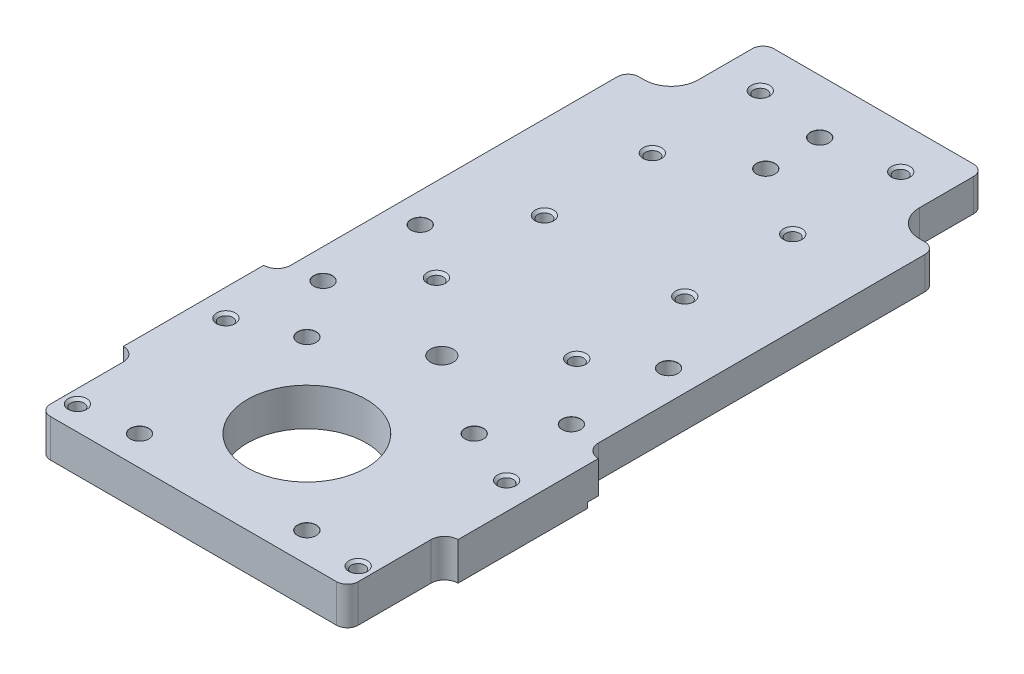
SolidWorks part; units mm, degrees
ref_plane "Top" through (0, 0, 0) normal (0, 0, 1) x (1, 0, 0)
ref_plane "Front" through (0, 0, 0) normal (0, 1, 0) x (1, 0, 0)
ref_plane "Right" through (0, 0, 0) normal (1, 0, 0) x (0, 0, -1)
sketch "Plate Main Sketch" plane through (-158.0855, 0, 24.6791) normal (0, 1, 0) x (-1, 0, 0)
  line L1 (-178.5855, -24.6791) -> (-137.5855, -24.6791)
  line L2 (-127.0855, 57.3209) -> (-127.0855, 83.3209)
  line L3 (-129.5855, 101.3209) -> (-186.5855, 101.3209)
  line L4 (-129.5855, 101.3209) -> (-129.5855, 85.8209)
  line L5 (-158.0855, 101.3209) -> (-158.0855, -24.6791) construction
  line L6 (-178.5855, -12.6791) -> (-178.5855, -24.6791)
  line L7 (-129.5855, 54.8209) -> (-129.5855, -7.6791)
  line L8 (-129.5855, -7.6791) -> (-132.5855, -7.6791)
  line L9 (-137.5855, -12.6791) -> (-137.5855, -24.6791)
  line L10 (-186.5855, -7.6791) -> (-183.5855, -7.6791)
  line L11 (-186.5855, 54.8209) -> (-186.5855, -7.6791)
  line L12 (-189.0855, 57.3209) -> (-189.0855, 83.3209)
  line L13 (-186.5855, 101.3209) -> (-186.5855, 85.8209)
  arc A0 (-129.5855, 85.8209) -> (-127.0855, 83.3209) centre (-127.0855, 85.8209) ccw
  arc A1 (-129.5855, 54.8209) -> (-127.0855, 57.3209) centre (-127.0855, 54.8209) cw
  arc A2 (-132.5855, -7.6791) -> (-137.5855, -12.6791) centre (-132.5855, -12.6791) ccw
  arc A3 (-183.5855, -7.6791) -> (-178.5855, -12.6791) centre (-183.5855, -12.6791) cw
  arc A4 (-186.5855, 54.8209) -> (-189.0855, 57.3209) centre (-189.0855, 54.8209) ccw
  arc A5 (-186.5855, 85.8209) -> (-189.0855, 83.3209) centre (-189.0855, 85.8209) cw
  circle A18 centre (-158.0855, 80.3209) radius 11
  circle A19 centre (-158.0855, 55.3209) radius 2.1117
  point P27 (0, 0)
  dimension "D2" = 5
  dimension "D8" = 22
  dimension "D1" = 2.5
  dimension "D3" = 62
  dimension "D4" = 126
  dimension "D5" = 18
  dimension "D6" = 44
  dimension "D15" = 21
  dimension "D16" = 46
  dimension "D17" = 8
  dimension "D7" = 109
extrude "Extrude Plate Main" add sketch "Plate Main Sketch" along normal blind 7
fillet "Fillet1" radius 2 6 edges at (-28.5, 3.5, 126) (-28.5, 3.5, 17) (-20.5, 3.5, 0) (20.5, 3.5, 0) (28.5, 3.5, 17) (28.5, 3.5, 126)
sketch "Reccess Sketch" plane through (0, 0, 0) normal (0, 1, 0) x (1, 0, 0)
  line L0 (-8.25, 0) -> (-8.25, -81)
  line L1 (-11.25, -84) -> (-31, -84)
  line L2 (-31, -84) -> (-31, 0)
  line L3 (-31, 0) -> (-8.25, 0)
  line L4 (0, 0) -> (0, -84) construction
  line L5 (31, 0) -> (8.25, 0)
  line L6 (8.25, 0) -> (8.25, -81)
  line L7 (31, -84) -> (31, 0)
  line L8 (11.25, -84) -> (31, -84)
  arc A0 (-8.25, -81) -> (-11.25, -84) centre (-11.25, -81) cw
  arc A1 (8.25, -81) -> (11.25, -84) centre (11.25, -81) ccw
  point P7 (-8.25, -84)
  point P10 (0, 0)
  dimension "D4" = 3
  dimension "D1" = 84
  dimension "D2" = 31
  dimension "D3" = 22.75
hole_wizard "M3x0.5 Tapped Hole3" positions "Sketch12" profile "Sketch13" tap size "M3x0.5" standard "ANSI Metric" end condition through all
sketch "Sketch12" plane through (0, 0, 0) normal (0, -1, 0) x (-1, 0, 0)
  line L0 (-13, -8) -> (-13, -68) construction
  line L2 (13, -68) -> (13, -8) construction
  line L4 (26, -121.5) -> (-26, -121.5) construction
  line L5 (-26, -121.5) -> (-26, -94) construction
  line L6 (-26, -94) -> (26, -94) construction
  line L7 (26, -94) -> (26, -121.5) construction
  line L11 (31, -126) -> (-31, -126) construction
  line L12 (31, -126) -> (31, 0) construction
  line L13 (31, 0) -> (-31, 0) construction
  line L14 (-31, -126) -> (-31, 0) construction
  line L15 (0, 0) -> (0, -126) construction
  line L16 (31, -63) -> (-31, -63) construction
  point P0 (-26, -121.5)
  point P2 (-26, -94)
  point P4 (26, -94)
  point P8 (13, -68)
  point P10 (13, -48)
  point P12 (13, -28)
  point P14 (13, -8)
  point P16 (-13, -8)
  point P18 (-13, -28)
  point P20 (-13, -48)
  point P22 (-13, -68)
  point P477 (26, -121.5)
  point P479 (0, 0)
  point P481 (0, 0)
  point P482 (0, 0)
  point P483 (0, 0)
  point P484 (0, 0)
  point P485 (0, -63)
  point P486 (0, 0)
  point P487 (21.3881, -116.3693)
  point P488 (0, 0)
  point P489 (0, 0)
  dimension "D1" = 126
  dimension "D2" = 62
  dimension "D3" = 118
  dimension "D4" = 98
  dimension "D5" = 78
  dimension "D6" = 58
  dimension "D7" = 18
  dimension "D8" = 18
  dimension "D9" = 5
  dimension "D10" = 5
  dimension "D11" = 4.5
  dimension "D12" = 32
sketch "Sketch13" plane through (26, 0, 121.5) normal (1, 0, 0) x (0, 0, -1)
  line L0 (0, 0) -> (0, 7)
  line L1 (0, 7) -> (1.725, 7)
  line L2 (1.25, 6.525) -> (1.25, 0)
  line L5 (1.25, 0) -> (0, 0)
  line L7 (1.725, 7) -> (1.25, 6.525)
  line L8 (-1.725, 7) -> (-1.25, 6.525) construction
  line L11 (0, -6.35) -> (0, 107.95) construction
  dimension "Thru Tap Drill Dia." = 2.5
  dimension "Thru Tap Drill Depth" = 7
  dimension "Far C'Sink Dia." = 3.45
  dimension "Far C'Sink Angle" = 90
cosmetic thread "Hole Thread54" parameters "D2"=3
cosmetic thread "Hole Thread55" parameters "D2"=3
cosmetic thread "Hole Thread56" parameters "D2"=3
cosmetic thread "Hole Thread57" parameters "D2"=3
cosmetic thread "Hole Thread58" parameters "D2"=3
cosmetic thread "Hole Thread59" parameters "D2"=3
cosmetic thread "Hole Thread60" parameters "D2"=3
cosmetic thread "Hole Thread61" parameters "D2"=3
cosmetic thread "Hole Thread62" parameters "D2"=3
cosmetic thread "Hole Thread63" parameters "D2"=3
cosmetic thread "Hole Thread64" parameters "D2"=3
cosmetic thread "Hole Thread65" parameters "D2"=3
hole_wizard "CBORE for M3 SHCS1" positions "Sketch4" profile "Sketch5" counterbore size "M3" standard "ANSI Metric" end condition through all
sketch "Sketch4" plane through (0, 0, 0) normal (0, -1, 0) x (-1, 0, 0)
  line L0 (31, -126) -> (-31, -126) construction
  line L1 (-31, -126) -> (-31, 0) construction
  line L2 (-31, 0) -> (31, 0) construction
  line L3 (31, 0) -> (31, -126) construction
  line L5 (15.5, -120.5) -> (-15.5, -120.5) construction
  line L6 (-15.5, -120.5) -> (-15.5, -89.5) construction
  line L7 (-15.5, -89.5) -> (15.5, -89.5) construction
  line L8 (15.5, -89.5) -> (15.5, -120.5) construction
  line L10 (0, -126) -> (0, 0) construction
  point P0 (15.5, -120.5)
  point P3 (-15.5, -120.5)
  point P6 (-15.5, -89.5)
  point P9 (15.5, -89.5)
  point P12 (23, -79)
  point P15 (-23, -79)
  point P18 (-23, -61)
  point P21 (23, -61)
  point P24 (0, -20)
  point P27 (0, -10)
  point P42 (0, 0)
  point P65 (0, -120.5)
  point P66 (0, 0)
  point P67 (0, 0)
  point P68 (0, 0)
  point P69 (0, 0)
  point P70 (-6.881, -20.0656)
  point P71 (-4.9364, -10.8138)
  point P72 (0, 0)
  point P73 (0, 0)
  dimension "D1" = 126
  dimension "D2" = 62
  dimension "D3" = 31
  dimension "D4" = 31
  dimension "D5" = 5.5
  dimension "D6" = 47
  dimension "D7" = 65
  dimension "D8" = 106
  dimension "D9" = 116
  dimension "D10" = 8
  dimension "D11" = 8
sketch "Sketch5" plane through (-15.5, 0, 120.5) normal (1, 0, 0) x (0, 0, -1)
  line L0 (0, 0) -> (0, 7)
  line L1 (1.7, 6.975) -> (1.725, 7)
  line L2 (1.7, 6.975) -> (1.7, 4.5)
  line L3 (1.7, 4.5) -> (3, 4.5)
  line L4 (3, 4.5) -> (3, 0)
  line L5 (3, 0) -> (0, 0)
  line L11 (0, -6.35) -> (0, 107.95) construction
  line L12 (1.725, 7) -> (0, 7)
  line L13 (-1.7, 6.975) -> (-1.725, 7) construction
  dimension "Thru Hole Dia." = 3.4
  dimension "Thru Hole Depth" = 7
  dimension "C'Bore Dia." = 6
  dimension "C'Bore Depth" = 4.5
  dimension "Far C'Sink Dia." = 3.45
  dimension "Far C'Sink Angle" = 90
extrude "Cut Recess" cut sketch "Reccess Sketch" along normal blind 1
sketch "Sketch7" plane through (158.0855, -24.6791, 0) normal (0, 0, -1) x (1, 0, 0)
  line L1 (-178.5855, -24.6791) -> (-137.5855, -24.6791) construction
  line L2 (-127.0855, 57.3209) -> (-127.0855, 83.3209) construction
  line L3 (-129.5855, 101.3209) -> (-186.5855, 101.3209) construction
  line L4 (-129.5855, 101.3209) -> (-129.5855, 85.8209) construction
  line L5 (-158.0855, 101.3209) -> (-158.0855, -24.6791) construction
  line L6 (-178.5855, -12.4678) -> (-178.5855, -24.6791) construction
  line L7 (-129.5855, 54.8209) -> (-129.5855, -7.6791) construction
  line L8 (-129.5855, -7.6791) -> (-132.7968, -7.6791) construction
  line L9 (-137.5855, -12.4678) -> (-137.5855, -24.6791) construction
  line L10 (-186.5855, -7.6791) -> (-183.3743, -7.6791) construction
  line L11 (-186.5855, 54.8209) -> (-186.5855, -7.6791) construction
  line L12 (-189.0855, 57.3209) -> (-189.0855, 83.3209) construction
  line L13 (-186.5855, 101.3209) -> (-186.5855, 85.8209) construction
  line L14 (-173.5855, 95.8209) -> (-142.5855, 95.8209) construction
  line L15 (-142.5855, 95.8209) -> (-142.5855, 64.8209) construction
  line L16 (-142.5855, 64.8209) -> (-173.5855, 64.8209) construction
  line L17 (-173.5855, 64.8209) -> (-173.5855, 95.8209) construction
  arc A0 (-129.5855, 85.8209) -> (-127.0855, 83.3209) centre (-127.0855, 85.8209) ccw construction
  arc A1 (-129.5855, 54.8209) -> (-127.0855, 57.3209) centre (-127.0855, 54.8209) cw construction
  arc A2 (-132.7968, -7.6791) -> (-137.5855, -12.4678) centre (-132.7968, -12.4678) ccw construction
  arc A3 (-183.3743, -7.6791) -> (-178.5855, -12.4678) centre (-183.3743, -12.4678) cw construction
  arc A4 (-186.5855, 54.8209) -> (-189.0855, 57.3209) centre (-189.0855, 54.8209) ccw construction
  arc A5 (-186.5855, 85.8209) -> (-189.0855, 83.3209) centre (-189.0855, 85.8209) cw construction
  circle A6 centre (-142.5855, 95.8209) radius 0.8649
  circle A7 centre (-142.5855, 64.8209) radius 0.8649
  circle A8 centre (-173.5855, 64.8209) radius 0.8649
  circle A9 centre (-173.5855, 95.8209) radius 0.8649
  circle A20 centre (-158.0855, -4.6791) radius 0.9359
  circle A21 centre (-158.0855, -14.6791) radius 1.008
  circle A22 centre (-176.6802, 54.3209) radius 1.5374
  circle A23 centre (-176.6802, 36.3209) radius 1.5374
  circle A24 centre (-142.5855, 54.3209) radius 1.5374
  circle A25 centre (-142.5855, 36.3209) radius 1.5374
  dimension "D3" = 62
  dimension "D1" = 2.5
  dimension "D2" = 15.5
  dimension "D8" = 106
  dimension "D11" = 116
  dimension "D12" = 47
  dimension "D4" = 126
  dimension "D5" = 18
  dimension "D6" = 44
  dimension "D7" = 109
  dimension "D9" = 5.5
  dimension "D10" = 36.5
  dimension "D13" = 65
  dimension "D17" = 8
equation "\"M2 Close Fit Hole\"= 2.2"
equation "\"M2.5 Close Fit Hole\"= 2.7"
equation "\"M3 Close Fit Hole\"= 3.2"
equation "\"M4 Close Fit Hole\"= 4.3"
equation "\"M5 Close Fit Hole\"= 5.3"
equation "\"M6 Close Fit Hole\"= 6.3"
equation "\"M7 Close Fit Hole\"= 7.4"
equation "\"M8 Close Fit Hole\"= 8.4"
equation "\"M2 Tap Hole 75%\"= 1.6"
equation "\"M3 Tap Hole 75%\"= 2.5"
equation "\"M4 Tap Hole 75%\"= 3.3"
equation "\"M5 Tap Hole 75%\"= 4.2"
equation "\"M6 Tap Hole 75%\"= 5"
equation "\"M7 Tap Hole 75%\"= 6"
equation "\"M8 Tap Hole 75%\"= 6.8"
equation "\"Bracket Width\"= 62mm"
equation "\"D3@Plate Main Sketch\"=\"Bracket Width\""
equation "\"Bracket Height\"= 126mm"
equation "\"D4@Plate Main Sketch\"=\"Bracket Height\""
equation "\"D1@Sketch4\"=\"Bracket Height\""
equation "\"D2@Sketch4\"=\"Bracket Width\""
equation "\"D1@Sketch12\"=\"Bracket Height\""
equation "\"D2@Sketch12\"=\"Bracket Width\""
equation "\"D2@Reccess Sketch\" = 0.5 * \"Bracket Width\""
